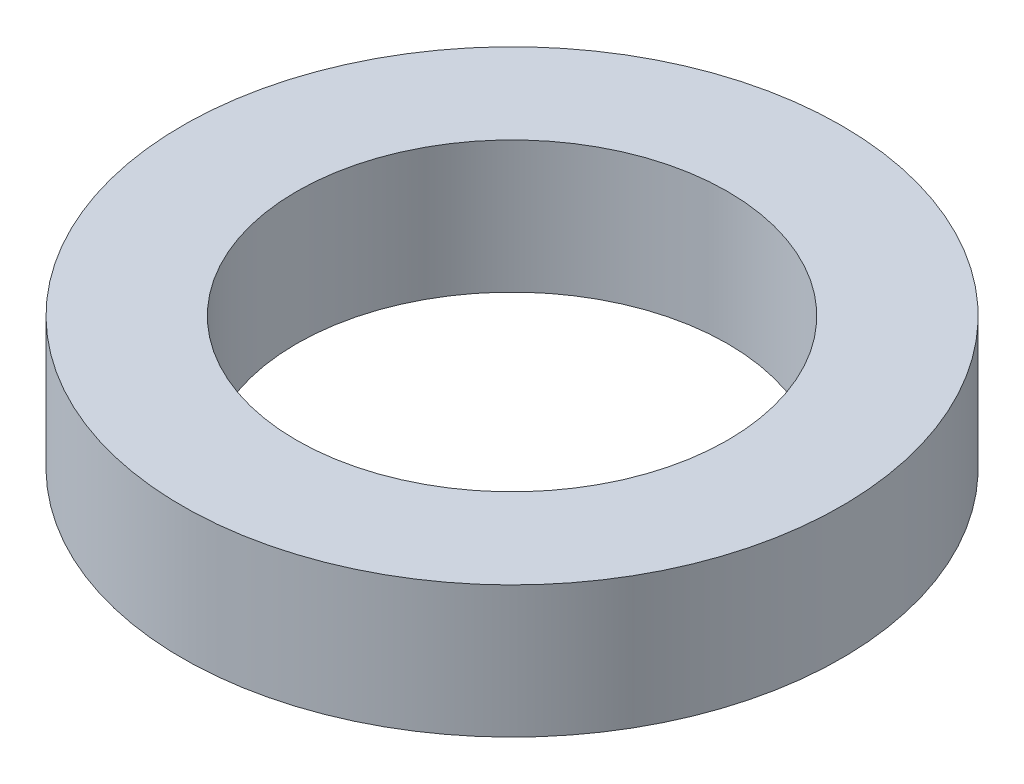
SolidWorks part; units mm, degrees
ref_plane "Front Plane" through (0, 0, 0) normal (0, 0, 1) x (1, 0, 0)
ref_plane "Top Plane" through (0, 0, 0) normal (0, 1, 0) x (1, 0, 0)
ref_plane "Right Plane" through (0, 0, 0) normal (1, 0, 0) x (0, 0, -1)
sketch "Sketch1" plane through (0, 0, 0) normal (0, 1, 0) x (1, 0, 0)
  circle A0 centre (0, 0) radius 65
  dimension "FLANGE_OD" = 130
extrude "Boss-Extrude1" add sketch "Sketch1" along normal blind 26
sketch "Sketch2" plane through (0, 0, 0) normal (0, 1, 0) x (1, 0, 0)
  circle A0 centre (0, 0) radius 42.5
  dimension "BORE_D" = 85
extrude "Cut-Extrude1" cut sketch "Sketch2" along normal through all
sketch "Sketch3" plane through (0, 26, 0) normal (0, 1, 0) x (1, 0, 0)
  circle A0 centre (0, 0) radius 28.6601 construction
  circle A1 centre (-28.6601, 0) radius 2.8759
  dimension "BOLT_D" = 5.7518
  dimension "BOLT_PCD" = 57.3201
extrude "Cut-Extrude2" cut sketch "Sketch3" against normal blind 24.7747 rebuild error yes
pattern_circular "CirPattern1" count 4 over 360 rebuild error yes
